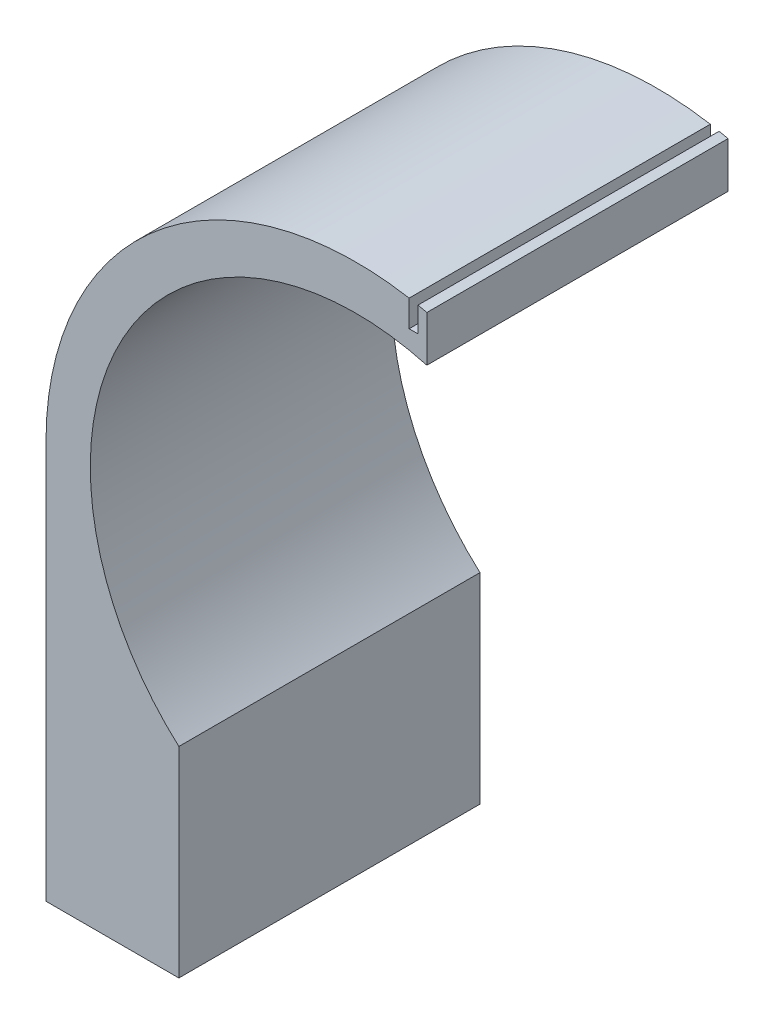
SolidWorks part; units mm, degrees
material "201 Annealed Stainless Steel (SS)"
ref_plane "Front Plane" through (0, 0, 0) normal (0, 0, 1) x (1, 0, 0)
ref_plane "Top Plane" through (0, 0, 0) normal (0, 1, 0) x (1, 0, 0)
ref_plane "Right Plane" through (0, 0, 0) normal (1, 0, 0) x (0, 0, -1)
sketch "Sketch1" plane through (0, 0, 0) normal (0, 0, 1) x (1, 0, 0)
  line L0 (0, 0) -> (0, -175) construction
  line L1 (-100, -111.8034) -> (-100, -225)
  line L2 (0, 0) -> (101.5936, 0) construction
  line L3 (40, 113.7839) -> (40, -22.985) construction
  line L5 (40, 170.3673) -> (40, 144.5683)
  line L7 (0, 0) -> (-138.7196, 0) construction
  line L8 (-175, 0) -> (-175, -225)
  line L9 (-100, -225) -> (-175, -225)
  line L10 (0, -175) -> (0, -225) construction
  line L11 (0, -225) -> (-200, -225) construction
  line L12 (-100, -111.8034) -> (100, -111.8034) construction
  line L13 (0, -150) -> (-100, -150) construction
  line L14 (35, 171.4643) -> (35, 157.4094)
  line L15 (35, 157.4094) -> (30, 157.4094)
  line L16 (30, 157.4094) -> (30, 172.4094)
  circle A0 centre (0, 0) radius 150 construction
  circle A1 centre (0, 0) radius 175 construction
  arc A2 (-100, -111.8034) -> (40, 144.5683) centre (0, 0) cw
  arc A3 (-175, 0) -> (30, 172.4094) centre (0, 0) cw
  arc A4 (35, 171.4643) -> (40, 170.3673) centre (0, 0) cw
  dimension "D1" = 300
  dimension "D2" = 350
  dimension "D6" = 175
  dimension "D5" = 50
  dimension "D3" = 5
  dimension "D4" = 30
  dimension "D7" = 200
  dimension "D8" = 5
  dimension "D9" = 15
extrude "Inner Ring - Left Side" add sketch "Sketch1" along normal blind 170
sketch "Sketch2" plane through (-100, 0, 0) normal (1, 0, 0) x (0, 0, -1)
  line L0 (0, -150) -> (-170, -150) construction
  line L1 (-170, -225) -> (-170, -111.8034) construction
